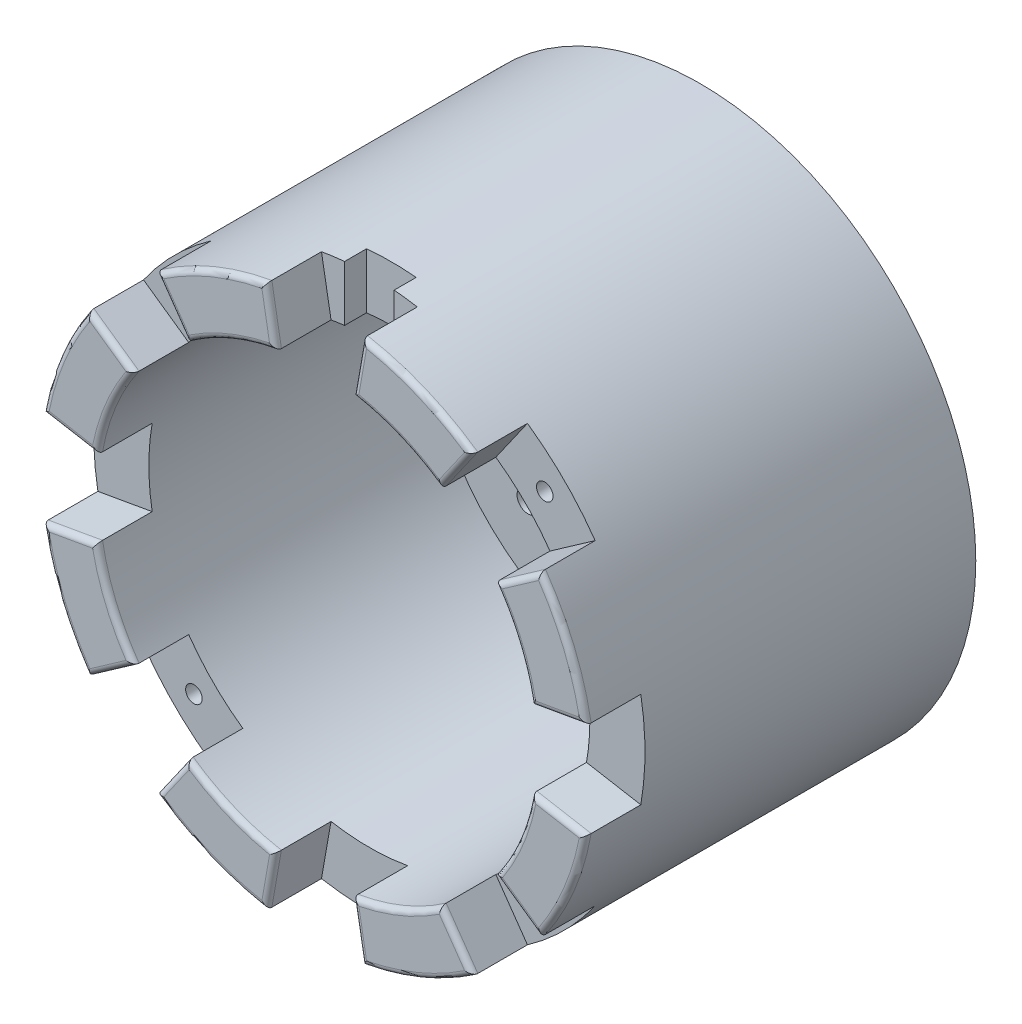
SolidWorks part; units mm, degrees
ref_plane "Alzado" through (0, 0, 0) normal (0, 0, 1) x (1, 0, 0)
ref_plane "Planta" through (0, 0, 0) normal (0, 1, 0) x (1, 0, 0)
ref_plane "Vista lateral" through (0, 0, 0) normal (1, 0, 0) x (0, 0, -1)
sketch "Croquis1" plane through (0, 0, 0) normal (0, 0, 1) x (1, 0, 0)
  circle A0 centre (0, 0) radius 50
  circle A1 centre (0, 0) radius 15.5
  point P4 (0, 0)
  dimension "D1" = 100
  dimension "D2" = 31
extrude "Saliente-Extruir1" add sketch "Croquis1" along normal blind 70
sketch "Croquis2" plane through (0, 0, 70) normal (0, 0, 1) x (1, 0, 0)
  circle A0 centre (0, 0) radius 40
  dimension "D1" = 80
extrude "Cortar-Extruir1" cut sketch "Croquis2" against normal blind 50
sketch "Croquis3" plane through (0, 0, 0) normal (0, 0, -1) x (-1, 0, 0)
  circle A0 centre (0, 0) radius 17.5
  dimension "D1" = 35
extrude "Cortar-Extruir2" cut sketch "Croquis3" against normal blind 10
sketch "Croquis4" plane through (0, 0, 20) normal (0, 0, 1) x (1, 0, 0)
  line L1 (-2.5, 32.5) -> (2.5, 32.5)
  line L2 (-2.5, 32.5) -> (-2.5, 22.5)
  line L3 (-2.5, 22.5) -> (2.5, 22.5)
  line L4 (2.5, 32.5) -> (2.5, 22.5)
  line L5 (-2.5, 32.5) -> (2.5, 22.5) construction
  line L6 (-2.5, 22.5) -> (2.5, 32.5) construction
  line L7 (32.5, -2.5) -> (22.5, -2.5)
  line L8 (32.5, -2.5) -> (32.5, 2.5)
  line L9 (32.5, 2.5) -> (22.5, 2.5)
  line L10 (22.5, -2.5) -> (22.5, 2.5)
  line L11 (32.5, -2.5) -> (22.5, 2.5) construction
  line L12 (32.5, 2.5) -> (22.5, -2.5) construction
  line L13 (2.5, -32.5) -> (-2.5, -32.5)
  line L14 (2.5, -32.5) -> (2.5, -22.5)
  line L15 (2.5, -22.5) -> (-2.5, -22.5)
  line L16 (-2.5, -32.5) -> (-2.5, -22.5)
  line L17 (2.5, -32.5) -> (-2.5, -22.5) construction
  line L18 (2.5, -22.5) -> (-2.5, -32.5) construction
  line L19 (-32.5, -2.5) -> (-22.5, -2.5)
  line L20 (-32.5, -2.5) -> (-32.5, 2.5)
  line L21 (-32.5, 2.5) -> (-22.5, 2.5)
  line L22 (-22.5, -2.5) -> (-22.5, 2.5)
  line L23 (-32.5, -2.5) -> (-22.5, 2.5) construction
  line L24 (-32.5, 2.5) -> (-22.5, -2.5) construction
  circle A0 centre (0, 0) radius 40
  circle A1 centre (0, 0) radius 27.5
  point P4 (0, 27.5)
  point P9 (27.5, 0)
  point P14 (0, -27.5)
  point P19 (-27.5, 0)
  circle M10 centre (0, 0) radius 15.5
  circle M11 centre (0, 0) radius 40
  dimension "D1" = 80
  dimension "D2" = 55
  dimension "D3" = 10
  dimension "D4" = 5
  dimension "D5" = 5
  dimension "D6" = 10
  dimension "D7" = 5
  dimension "D8" = 10
  dimension "D9" = 5
  dimension "D10" = 10
extrude "Cortar-Extruir3" cut sketch "Croquis4" against normal blind 10 contours A1 L9 L8 L7 L14 L13 L16 L19 L20 L21 L2 L1 L4 M11 | L9 A1 L4 L3 L2 L21 L22 L19 L16 L15 L14 L7 L10 M10 region at (-3.2746, 24.9431, 20) region at (-38.8686, 0, 20)
sketch "Croquis5" plane through (0, 0, 10) normal (0, 0, 1) x (1, 0, 0)
  line L0 (0, 0) -> (28.2843, 28.2843) construction
  circle A0 centre (21.2132, 21.2132) radius 2
  circle A1 centre (21.2132, -21.2132) radius 2
  circle A2 centre (-21.2132, -21.2132) radius 2
  circle A3 centre (-21.2132, 21.2132) radius 2
  point P14 (0, 0)
  dimension "D2" = 4
  dimension "D1" = 40
  dimension "D4" = 30
  dimension "D3" = 4
extrude "Cortar-Extruir4" cut sketch "Croquis5" against normal through all
sketch "Croquis6" plane through (0, 0, 0) normal (0, 0, -1) x (-1, 0, 0)
  circle A0 centre (-21.2132, 21.2132) radius 5
  circle A1 centre (21.487, 21.487) radius 5
  circle A2 centre (21.7607, -21.2132) radius 5
  circle A3 centre (-20.9394, -21.487) radius 5
  point P12 (0.2738, 0)
  dimension "D1" = 10
  dimension "D2" = 4
extrude "Cortar-Extruir5" cut sketch "Croquis6" against normal blind 5
sketch "Croquis7" plane through (0, 0, 70) normal (0, 0, 1) x (1, 0, 0)
  line L0 (0, 0) -> (0, 50)
  line L1 (0, 0) -> (8.6824, 49.2404)
  line L2 (0, 0) -> (-8.6824, 49.2404)
  line L3 (0, 0) -> (40.9576, 28.6788)
  line L4 (0, 0) -> (28.6788, 40.9576)
  line L5 (0, 0) -> (49.2404, -8.6824)
  line L6 (0, 0) -> (49.2404, 8.6824)
  line L7 (0, 0) -> (28.6788, -40.9576)
  line L8 (0, 0) -> (40.9576, -28.6788)
  line L9 (0, 0) -> (-8.6824, -49.2404)
  line L10 (0, 0) -> (8.6824, -49.2404)
  line L11 (0, 0) -> (-40.9576, -28.6788)
  line L12 (0, 0) -> (-28.6788, -40.9576)
  line L13 (0, 0) -> (-49.2404, 8.6824)
  line L14 (0, 0) -> (-49.2404, -8.6824)
  line L15 (0, 0) -> (-28.6788, 40.9576)
  line L16 (0, 0) -> (-40.9576, 28.6788)
  circle A0 centre (0, 0) radius 50 construction
  circle A1 centre (0, 0) radius 40
  circle A2 centre (0, 0) radius 50
  point P27 (0, 0)
  circle M5 centre (0, 0) radius 40
  circle M6 centre (0, 0) radius 50
  dimension "D3" = 100
  dimension "D4" = 80
  dimension "D1" = 10
  dimension "D2" = 10
  dimension "D5" = 8
extrude "Cortar-Extruir6" cut sketch "Croquis7" against normal blind 10 contours L2 L0 M5 M6 | L1 L0 M5 M6 | L4 L3 M5 M6 | L6 L5 M5 M6 | L8 L7 M5 M6 | L16 L15 M5 M6 | L14 L13 M5 M6 | L12 L11 M5 M6 | L10 L9 M5 M6 region at (-3.9332, 44.9561, 70) region at (3.9332, 44.9561, 70) region at (31.7888, 31.7888, 70) region at (44.9561, 0, 70) region at (31.7888, -31.7888, 70) region at (0, -44.9561, 70) region at (-31.7888, -31.7888, 70) region at (-44.9561, 0, 70) region at (-31.7888, 31.7888, 70)
fillet "Redondeo2" radius 1 48 edges at (7.8142, 44.3163, 70) (19.1342, 46.194, 70) (25.8109, 36.8618, 70) (15.3073, 36.9552, 70) (36.8618, 25.8109, 70) (46.194, 19.1342, 70) (44.3163, 7.8142, 70) (36.9552, 15.3073, 70) (44.3163, -7.8142, 70) (46.194, -19.1342, 70) (36.8618, -25.8109, 70) (36.9552, -15.3073, 70) (19.1342, -46.194, 70) (7.8142, -44.3163, 70) (15.3073, -36.9552, 70) (25.8109, -36.8618, 70) (-7.8142, -44.3163, 70) (-19.1342, -46.194, 70) (-25.8109, -36.8618, 70) (-15.3073, -36.9552, 70) (-19.1342, 46.194, 70) (-7.8142, 44.3163, 70) (-15.3073, 36.9552, 70) (-25.8109, 36.8618, 70) (-36.8618, -25.8109, 70) (-46.194, -19.1342, 70) (-44.3163, -7.8142, 70) (-36.9552, -15.3073, 70) (-44.3163, 7.8142, 70) (-46.194, 19.1342, 70) (-36.8618, 25.8109, 70) (-36.9552, 15.3073, 70) (0, -22.5, 20) (2.5, -27.5, 20) (0, -32.5, 20) (-2.5, -27.5, 20) (-32.5, 0, 20) (-27.5, 2.5, 20) (-22.5, 0, 20) (-27.5, -2.5, 20) (22.5, 0, 20) (27.5, 2.5, 20) (32.5, 0, 20) (27.5, -2.5, 20) (0, 22.5, 20) (-2.5, 27.5, 20) (0, 32.5, 20) (2.5, 27.5, 20)
sketch "Croquis8" plane through (0, 0, 70) normal (0, 0, 1) x (1, 0, 0)
  line L0 (0, 0) -> (0, 52.9149) construction
  line L2 (-4.5, 55) -> (4.5, 55)
  line L3 (-4.5, 55) -> (-4.5, 35)
  line L4 (-4.5, 35) -> (4.5, 35)
  line L5 (4.5, 55) -> (4.5, 35)
  line L6 (-4.5, 55) -> (4.5, 35) construction
  line L7 (-4.5, 35) -> (4.5, 55) construction
  point P3 (0, 45)
  dimension "D1" = 9
  dimension "D2" = 20
  dimension "D3" = 45
extrude "Cortar-Extruir7" cut sketch "Croquis8" against normal blind 4 from offset 10 offset against normal yes
sketch "Croquis9" plane through (0, 0, 60) normal (0, 0, 1) x (1, 0, 0)
  line L0 (0, 0) -> (42.0938, 42.0938) construction
  line L1 (0, 0) -> (50, 0) construction
  circle A0 centre (31.8198, 31.8198) radius 1.5
  circle A2 centre (0, 0) radius 40 construction
  arc A3 (49.2404, -8.6824) -> (49.2404, 8.6824) centre (0, 0) ccw construction
  circle A4 centre (31.8198, -31.8198) radius 1.5
  circle A5 centre (-31.8198, -31.8198) radius 1.5
  circle A6 centre (-31.8198, 31.8198) radius 1.5
  point P20 (0, 0)
  dimension "D2" = 3
  dimension "D1" = 45
  dimension "D3" = 45
  dimension "D4" = 4
extrude "Cortar-Extruir8" cut sketch "Croquis9" against normal blind 20
